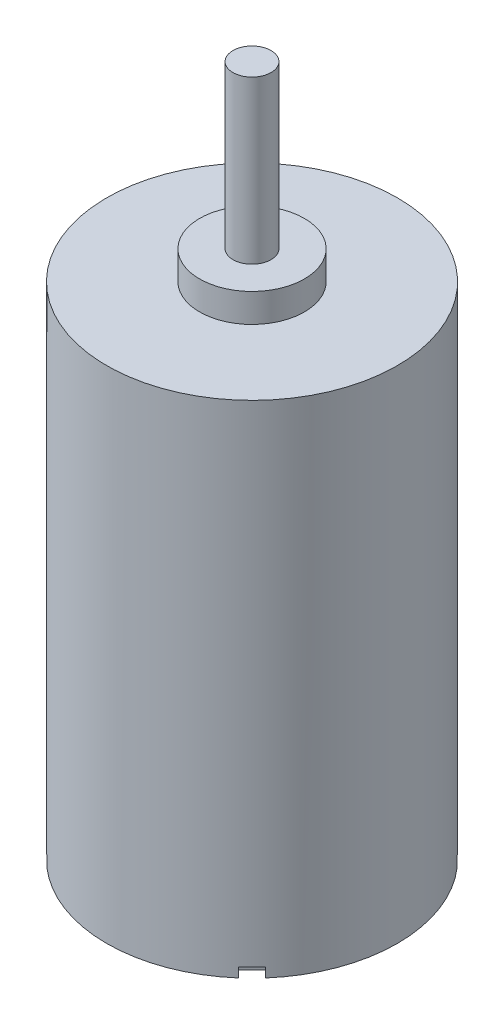
SolidWorks part; units mm, degrees
ref_plane "前视基准面" through (0, 0, 0) normal (0, 0, 1) x (1, 0, 0)
ref_plane "上视基准面" through (0, 0, 0) normal (0, 1, 0) x (1, 0, 0)
ref_plane "右视基准面" through (0, 0, 0) normal (1, 0, 0) x (0, 0, -1)
other "Configuration Table"
sketch "草图1" plane through (0, 0, 0) normal (1, 0, 0) x (0, 0, -1)
  line L1 (0, 0) -> (3.05, 0)
  line L2 (0, 0) -> (0, 10.5)
  line L3 (0, 10.5) -> (3.05, 10.5)
  line L4 (3.05, 0) -> (3.05, 10.5)
  line L5 (0, 10.5) -> (1.1, 10.5)
  line L6 (0, 10.5) -> (0, 11.1)
  line L7 (0, 11.1) -> (1.1, 11.1)
  line L8 (1.1, 10.5) -> (1.1, 11.1)
  line L9 (0, 11.1) -> (0.4, 11.1)
  line L10 (0, 11.1) -> (0, 14.5)
  line L11 (0, 14.5) -> (0.4, 14.5)
  line L12 (0.4, 11.1) -> (0.4, 14.5)
  dimension "D1" = 3.05
  dimension "D2" = 10.5
  dimension "D3" = 1.1
  dimension "D4" = 0.6
  dimension "D5" = 0.4
  dimension "D6" = 4
revolve "旋转1" add sketch "草图1" angle 360 about L10 region at (0, 5.25, -1.525) region at (0, 10.8, -0.55) region at (0, 12.8, -0.2)
sketch "草图2" plane through (0, 0, 0) normal (0, -1, 0) x (1, 0, 0)
  line L0 (-3.05, 0) -> (3.05, 0)
  line L1 (-1.8692, 2.152) -> (-2.152, 1.8692)
  line L2 (-2.152, 1.8692) -> (-2.2935, 2.0106)
  line L3 (-1.8692, 2.152) -> (-2.0106, 2.2935)
  line L4 (-2.0106, 2.0106) -> (0, 0)
  circle A0 centre (0, 0) radius 3.05 construction
  circle A1 centre (-2, 0) radius 0.25
  circle A2 centre (2, 0) radius 0.25
  circle M6 centre (0, 0) radius 3.05
  dimension "D6" = 0.5
  dimension "D1" = 45
  dimension "D2" = 0.2
  dimension "D3" = 0.4
  dimension "D4" = 1.05
  dimension "D5" = 1.05
extrude "切除-拉伸1" cut sketch "草图2" against normal blind 0.2 contours L1 L3 L2 M6 region at (-2.0829, 0, 2.0829)
pattern_circular "阵列(圆周)1" count 4 over 360 about axis through (0, 11.1, 0) along (0, -1, 0) of "切除-拉伸1" reverse direction yes
extrude "切除-拉伸2" cut sketch "草图2<3>" against normal blind 0.2 contours A1 | A2
sketch "草图2<3>" plane through (0, 0, 0) normal (0, -1, 0) x (1, 0, 0) same geometry as "草图2"
